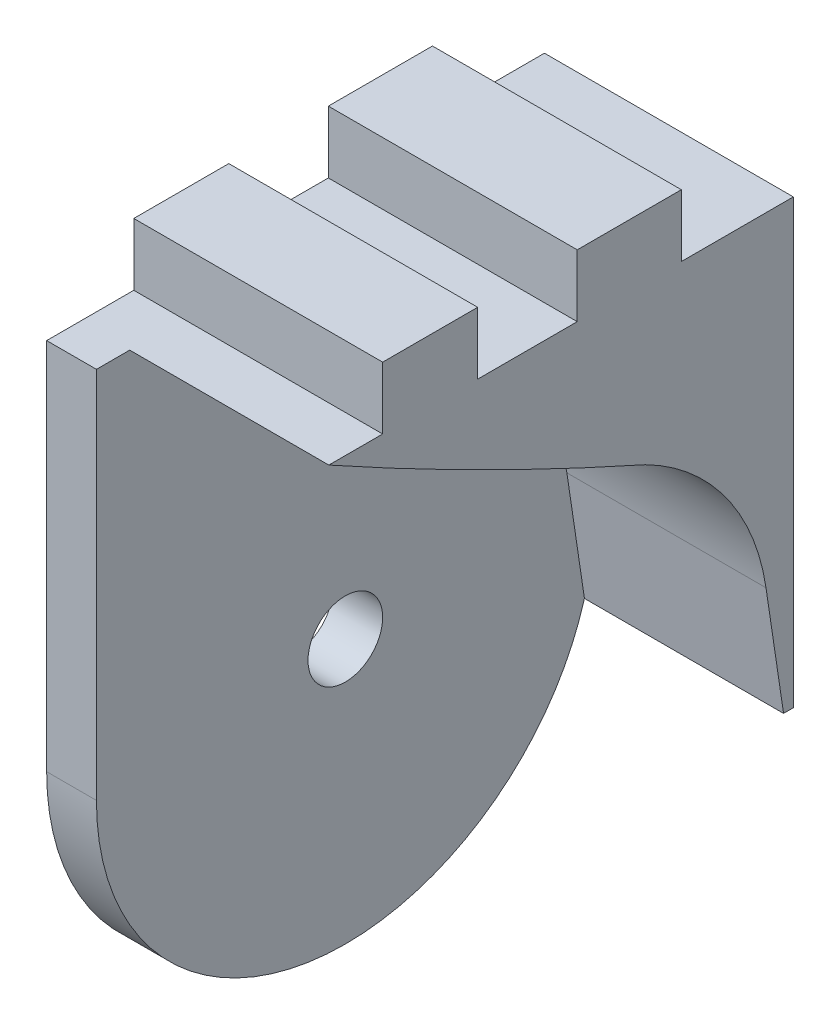
SolidWorks part; units mm, degrees
material "ABS"
ref_plane "Płaszczyzna przednia" through (0, 0, 0) normal (0, 0, 1) x (1, 0, 0)
ref_plane "Płaszczyzna górna" through (0, 0, 0) normal (0, 1, 0) x (1, 0, 0)
ref_plane "Płaszczyzna prawa" through (0, 0, 0) normal (1, 0, 0) x (0, 0, -1)
sketch "Szkic1" plane through (0, 0, 0) normal (0, 0, 1) x (1, 0, 0)
  line L0 (0, 0) -> (-4, 0)
  line L1 (-4, 55) -> (16, 55)
  line L2 (0, 0) -> (0, 51.5)
  line L3 (0, 51.5) -> (16, 51.5)
  line L5 (-4, 0) -> (-4, 55)
  line L9 (16, 55) -> (16, 51.5)
  dimension "D1" = 20
  dimension "D2" = 3.5
  dimension "D3" = 4
  dimension "D4" = 55
extrude "Dodanie-wyciągnięcie1" add sketch "Szkic1" along normal blind 40
fillet "Zaokrąglenie1" radius 20 2 edges at (-2, 0, 0) (-2, 0, 40)
sketch "Szkic5" plane through (-4, 0, 0) normal (-1, 0, 0) x (0, 0, 1)
  line L0 (0, 51.5) -> (40, 51.5) construction
  line L4 (40, 51.5) -> (11.8871, 37.3056)
  line L5 (0.7863, 14.4473) -> (2.1974, 23.8963)
  line L6 (0, 20) -> (0, 14.4473)
  line L7 (0, 14.4473) -> (0.7863, 14.4473)
  line L8 (0, 55) -> (0, 20) construction
  line L12 (0, 55) -> (0, 20)
  line L13 (40, 51.5) -> (40, 55)
  line L14 (40, 55) -> (0, 55)
  arc A0 (11.8871, 37.3056) -> (2.1974, 23.8963) centre (20, 21.2376) ccw
  circle A2 centre (20, 21.2376) radius 17.5
  arc A6 (0, 20) -> (0.7863, 14.4473) centre (20, 20) ccw
  arc A7 (40, 51.5) -> (11.8871, 37.3056) centre (-121.1931, 335.8163) cw
  arc M7 (0, 20) -> (20, 0) centre (20, 20) ccw
  dimension "D1" = 35
  dimension "D2" = 18
  dimension "D4" = 326.8317
  dimension "D5" = 0.7863
  dimension "D7" = 11.8871
  dimension "D8" = 14.4473
  dimension "D3" = 20
  dimension "D6" = 2.1974
  dimension "D14" = 55
extrude "Dodanie-wyciągnięcie2" add sketch "Szkic5" against normal blind 20 contours L6 L7 M7 | L0 L12 L5 A0 L4 M7 | A7 L4 region at (-4, 42.8778, 12.1376) region at (-4, 44.2673, 26.012) region at (-4, 15.83, 0.2351)
ref_plane "Płaszczyzna1" through (0, 47, 0) normal (0, 1, 0) x (1, 0, 0)
sketch "Szkic6" plane through (-4, 0, 0) normal (-1, 0, 0) x (0, 0, 1)
  line L1 (20, 55) -> (20, 0) construction
  line L2 (40, 55) -> (0, 55) construction
  circle A0 centre (20, 21.2376) radius 3
  arc A2 (11.8871, 37.3056) -> (2.1974, 23.8963) centre (20, 21.2376) ccw construction
extrude "Wytnij-wyciągnięcie1" cut sketch "Szkic6" against normal blind 10
sketch "Szkic8" plane through (-4, 0, 0) normal (-1, 0, 0) x (0, 0, 1)
  line L0 (0, 50) -> (9, 50)
  line L1 (0, 55) -> (0, 14.4473) construction
  line L2 (9, 50) -> (9, 55)
  line L3 (40, 55) -> (0, 55) construction
  line L4 (9, 55) -> (17.366, 55)
  line L5 (17.366, 55) -> (17.366, 50)
  line L6 (17.366, 50) -> (25.366, 50)
  line L7 (25.366, 50) -> (25.366, 55)
  line L8 (25.366, 55) -> (33, 55)
  line L9 (33, 55) -> (33, 50)
  line L10 (33, 50) -> (40, 50)
  line L11 (40, 55) -> (40, 20) construction
  line L12 (40, 50) -> (40, 57.0743)
  line L13 (40, 57.0743) -> (0, 57.0743)
  line L14 (0, 57.0743) -> (0, 50)
  point P8 (9, 52.5)
  point P17 (4.5, 50)
  dimension "D1" = 9
  dimension "D2" = 5
  dimension "D3" = 8
  dimension "D4" = 7
extrude "Wytnij-wyciągnięcie2" cut sketch "Szkic8" against normal through all
